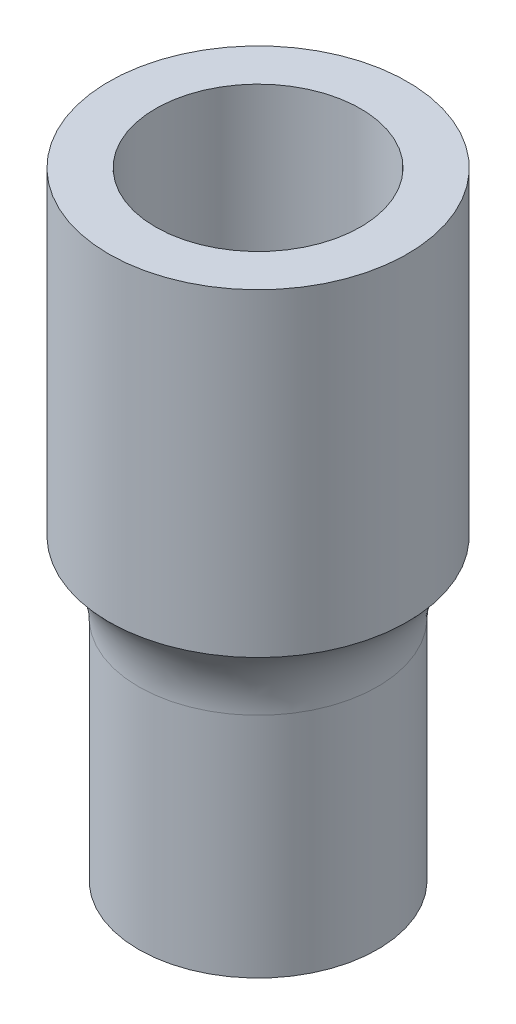
SolidWorks part; units mm, degrees
ref_plane "Front Plane" through (0, 0, 0) normal (0, 0, 1) x (1, 0, 0)
ref_plane "Top Plane" through (0, 0, 0) normal (0, 1, 0) x (1, 0, 0)
ref_plane "Right Plane" through (0, 0, 0) normal (1, 0, 0) x (0, 0, -1)
sketch "Sketch1" plane through (0, 0, 0) normal (0, 1, 0) x (1, 0, 0)
  circle A0 centre (0, 0) radius 4
  circle A1 centre (0, 0) radius 6
  dimension "D1" = 8
  dimension "D2" = 12
extrude "Boss-Extrude1" add sketch "Sketch1" along normal blind 15
sketch "Sketch2" plane through (0, 15, 0) normal (0, 1, 0) x (1, 0, 0)
  circle A0 centre (0, 0) radius 7.5
  dimension "D1" = 15
extrude "Boss-Extrude2" add sketch "Sketch2" along normal blind 16
fillet "Fillet1" radius 5 1 edges at (0, 15, 6)
sketch "Sketch3" plane through (0, 31, 0) normal (0, 1, 0) x (1, 0, 0)
  circle A0 centre (0, 0) radius 5.15
  dimension "D1" = 10.3
extrude "Cut-Extrude1" cut sketch "Sketch3" against normal blind 10
